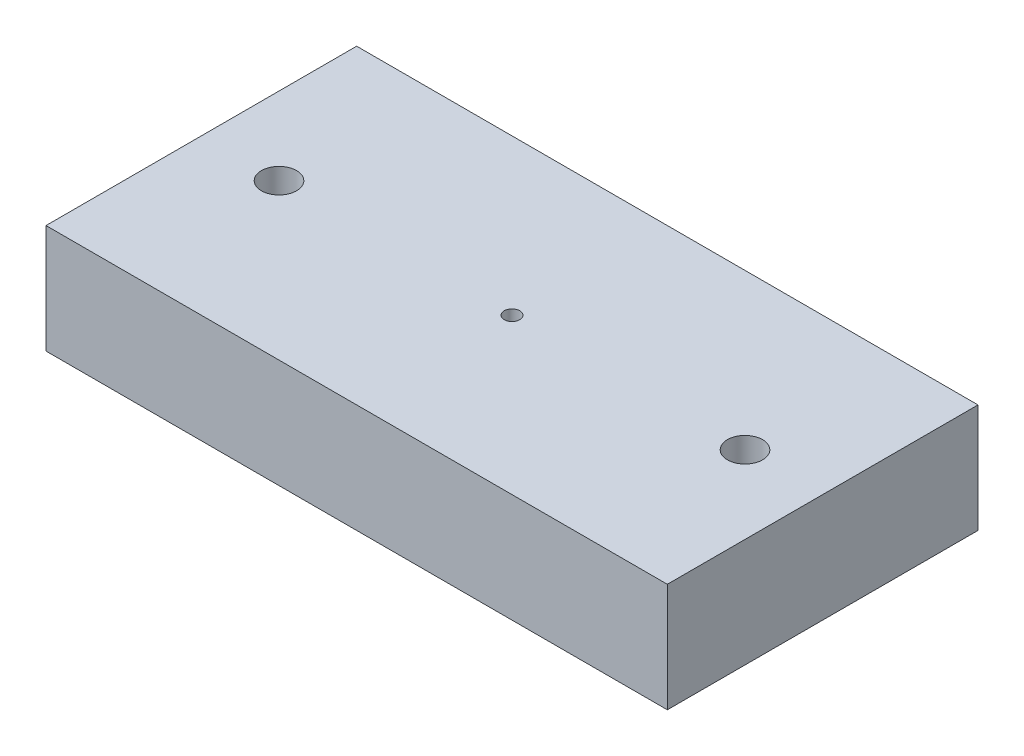
SolidWorks part; units mm, degrees
ref_plane "Front Plane" through (0, 0, 0) normal (0, 0, 1) x (1, 0, 0)
ref_plane "Top Plane" through (0, 0, 0) normal (0, 1, 0) x (1, 0, 0)
ref_plane "Right Plane" through (0, 0, 0) normal (1, 0, 0) x (0, 0, -1)
sketch "Sketch1" plane through (0, 0, 0) normal (0, 1, 0) x (1, 0, 0)
  line L1 (-20, -10) -> (20, -10)
  line L2 (-20, -10) -> (-20, 10)
  line L3 (-20, 10) -> (20, 10)
  line L4 (20, -10) -> (20, 10)
  line L5 (-20, -10) -> (20, 10) construction
  line L6 (-20, 10) -> (20, -10) construction
  point P0 (0, 0)
extrude "Boss-Extrude1" add sketch "Sketch1" along normal blind 7
sketch "Sketch2" plane through (0, 7, 0) normal (0, 1, 0) x (1, 0, 0)
  circle A0 centre (0, 0) radius 0.5
extrude "Cut-Extrude1" cut sketch "Sketch2" against normal blind 6.72
hole_wizard "#4-40 Tapped Hole1" positions "3DSketch4" profile "Sketch9" tap size "#4-40" standard "ANSI Inch" end condition through all
sketch3d "3DSketch4"
  point P0 (-15, 0, 0)
cosmetic thread "Hole Thread1" parameters "D2"=2.8448
sketch "Sketch9" plane through (-15, 0, 0) normal (1, 0, 0) x (0, 0, -1)
  line L0 (0, 0) -> (0, 7)
  line L1 (0, 7) -> (1.1303, 7)
  line L2 (1.1303, 7) -> (1.1303, 0.635)
  line L3 (1.1303, 0.635) -> (1.7653, 0)
  line L5 (1.7653, 0) -> (0, 0)
  line L6 (-1.1303, 0.635) -> (-1.7653, 0) construction
  line L11 (0, -6.35) -> (0, 107.95) construction
  dimension "Thru Tap Drill Dia." = 2.2606
  dimension "Thru Tap Drill Depth" = 7
  dimension "Near C'Sink Dia." = 3.5306
  dimension "Near C'Sink Angle" = 90
sketch "Sketch11" plane through (0, 0, 0) normal (0, -1, 0) x (1, 0, 0)
  line L0 (-20, 0) -> (20, 0) construction
  line L1 (-20, -10) -> (-20, 10) construction
  line L2 (20, 10) -> (20, -10) construction
pattern_linear "LPattern1" count 2 spacing 30 along (1, 0, 0) of "#4-40 Tapped Hole1"
sketch "Sketch12" plane through (0, 0, 0) normal (0, -1, 0) x (1, 0, 0)
  circle A0 centre (0, 0) radius 3.97
  circle A1 centre (0, 0) radius 5.55
extrude "Cut-Extrude2" cut sketch "Sketch12" against normal blind 4.9
sketch "Sketch13" plane through (0, 0, 0) normal (0, -1, 0) x (1, 0, 0)
  line L1 (-2.5, 1.75) -> (2.5, 1.75)
  line L2 (-2.5, 1.75) -> (-2.5, -1.75)
  line L3 (-2.5, -1.75) -> (2.5, -1.75)
  line L4 (2.5, 1.75) -> (2.5, -1.75)
  line L5 (-2.5, 1.75) -> (2.5, -1.75) construction
  line L6 (-2.5, -1.75) -> (2.5, 1.75) construction
extrude "Cut-Extrude3" cut sketch "Sketch13" against normal blind 0.5
